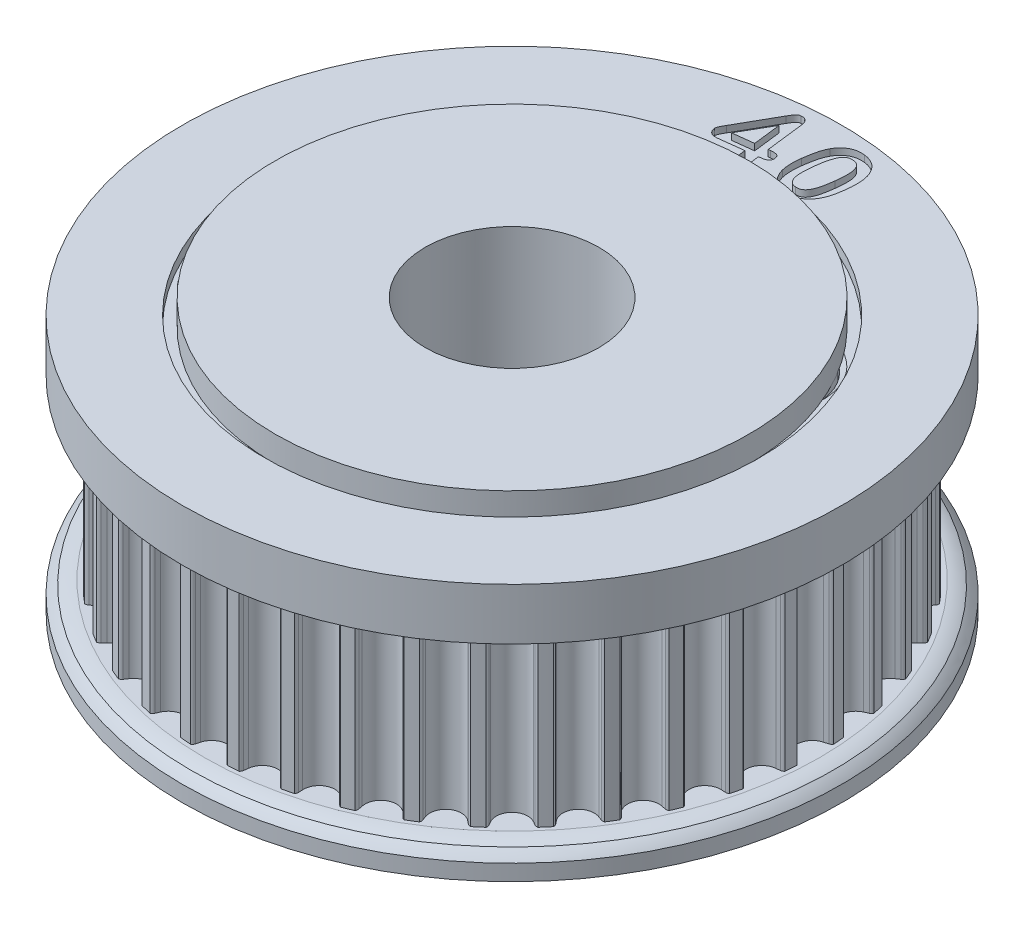
SolidWorks part; units mm, degrees
other "DetailItem2"
material "Markforged"
ref_plane "Front Plane" through (0, 0, 0) normal (0, 0, 1) x (1, 0, 0)
ref_plane "Top Plane" through (0, 0, 0) normal (0, 1, 0) x (1, 0, 0)
ref_plane "Right Plane" through (0, 0, 0) normal (1, 0, 0) x (0, 0, -1)
ref_axis "Centerline" through (0, 8.7312, 0) along (0, -1, 0)
sketch "Sketch1" plane through (0, 0, 0) normal (0, 1, 0) x (1, 0, 0)
  circle A0 centre (0, 0) radius 18.7176
  dimension "OuterDiameter" = 37.4352
extrude "ToothOD" add sketch "Sketch1" along normal mid plane 12.3825
sketch "Sketch2" plane through (0, 0, 0) normal (0, 1, 0) x (1, 0, 0)
  line L0 (0, 17.5492) -> (50000, 17.5492) construction
  line L1 (0, 18.7176) -> (50000, 18.7176) construction
  line L2 (0, 0) -> (0, 50000) construction
  arc A0 (-0.937, 18.2677) -> (0, 17.5492) centre (0, 18.5195) ccw
  arc A1 (-1.1278, 18.6836) -> (1.1278, 18.6836) centre (0, 0) cw
  circle A2 centre (0, 0) radius 18.7176 construction
  arc A3 (-0.937, 18.2677) -> (-1.0078, 18.5195) centre (-11.9754, 15.3012) ccw
  arc A4 (-1.0078, 18.5195) -> (-1.1278, 18.6836) centre (-1.2954, 18.4351) ccw
  circle A5 centre (0, 0) radius 18.7176 construction
  arc A6 (0.937, 18.2677) -> (1.0078, 18.5195) centre (11.9754, 15.3012) cw
  arc A7 (1.0078, 18.5195) -> (1.1278, 18.6836) centre (1.2954, 18.4351) cw
  arc A8 (0, 17.5492) -> (0.937, 18.2677) centre (0, 18.5195) ccw
  dimension "D1" = 1.9406
  dimension "D3" = 22.86
  dimension "D4" = 0.5994
  dimension "D2" = 1.1684
  dimension "D5" = 1.2954
extrude "ToothProfile" cut sketch "Sketch2" against normal through all both and the other way through all
pattern_circular "ToothPattern" count 40 over 360 about axis through (0, 6.1913, 0) along (0, -1, 0) of "ToothProfile"
sketch "Sketch4" plane through (0, 0, 0) normal (0, 0, 1) x (1, 0, 0)
  line L0 (0, -6.1913) -> (18.9716, -6.1913)
  line L1 (0, -7.9375) -> (20.32, -7.9375)
  line L2 (0, -7.9375) -> (0, -6.1913)
  line L3 (20.32, -7.9375) -> (20.32, -6.9532)
  line L4 (0, 0) -> (50000, 0) construction
  line L5 (20.32, 7.9375) -> (20.32, 6.9532)
  line L6 (0, 7.9375) -> (0, 6.1913)
  line L7 (0, 7.9375) -> (20.32, 7.9375)
  line L8 (0, 6.1913) -> (18.9716, 6.1913) construction
  line L9 (0, 6.1913) -> (0, 3.9688)
  line L10 (0, 3.9688) -> (18.9716, 3.9688)
  line L11 (18.9716, 3.9688) -> (20.32, 4.7473)
  line L12 (20.32, 4.7473) -> (20.32, 6.9532)
  line L13 (18.9716, 3.9688) -> (18.9716, 6.1913) construction
  arc A0 (18.9716, -6.1913) -> (19.812, -6.4452) centre (18.6641, -8.7261) cw
  arc A2 (19.812, -6.4452) -> (20.32, -6.9532) centre (17.815, -8.9503) cw
  arc A3 (19.812, 6.4452) -> (20.32, 6.9532) centre (17.815, 8.9503) ccw construction
  arc A4 (18.9716, 6.1913) -> (19.812, 6.4452) centre (18.6641, 8.7261) ccw construction
  dimension "D5" = 2.5534
  dimension "D6" = 3.2036
  dimension "FlangeID" = 18.9716
  dimension "D1" = 1.7463
  dimension "D2" = 0.9843
  dimension "D3" = 6.1913
  dimension "D4" = 15.875
  dimension "D7" = 0.762
  dimension "D8" = 0.508
  dimension "D10" = 0.508
  dimension "D9" = 20.32
  dimension "D11" = 10.16
  dimension "D12" = 30
revolve "Flange" add sketch "Sketch4" angle 360 about axis through (0, 8.7312, 0) along (0, -1, 0)
sketch "Sketch7" plane through (0, 0, 0) normal (0, -1, 0) x (1, 0, 0)
  circle A0 centre (0, 0) radius 5.3581
  dimension "D1" = 10.7163
extrude "Bore" cut sketch "Sketch7" against normal through all both and the other way through all
sketch "Sketch9" plane through (0, 7.9375, 0) normal (0, 1, 0) x (1, 0, 0)
  arc A0 (-10.7763, -10.7763) -> (10.7763, -10.7763) centre (0, 0) cw construction
  text T0 "40" font "Arial Rounded MT Bold" height 4.572
  point P3 (0, 15.24)
  dimension "D1" = 15.24
  dimension "D2" = 270
extrude "Large Tooth Count" cut sketch "Sketch9" against normal blind 0.4 and the other way through all
sketch "Sketch11" plane through (0, 7.9375, 0) normal (0, 1, 0) x (1, 0, 0)
  arc A0 (-4.8314, -4.8314) -> (4.8314, -4.8314) centre (0, 0) cw construction
  text T0 "<b>40</b>" font "Arial Rounded MT Bold" height 2.286
  point P6 (0, 6.8326)
  dimension "D4" = 6.8326
  dimension "D3" = 270
extrude "Small Tooth Count" [suppressed] cut sketch "Sketch11" against normal blind 0.4 and the other way through all
sketch "Sketch14" plane through (0, 0, 0) normal (0, 0, 1) x (1, 0, 0)
  line L0 (20.32, 7.9375) -> (-20.32, 7.9375) construction
  line L1 (0, 7.9375) -> (15.24, 7.9375)
  line L2 (0, 7.9375) -> (0, 7.3025)
  line L3 (0, 7.3025) -> (15.24, 7.3025)
  line L4 (15.24, 7.9375) -> (15.24, 7.3025)
  line L5 (0, 7.9375) -> (15.24, 7.3025) construction
  line L6 (0, 7.3025) -> (15.24, 7.9375) construction
  line L7 (-20.32, -7.9375) -> (20.32, -7.9375) construction
  line L8 (0, -7.9375) -> (15.24, -7.9375)
  line L9 (0, -7.9375) -> (0, -2.2225)
  line L10 (0, -2.2225) -> (15.24, -2.2225)
  line L11 (15.24, -7.9375) -> (15.24, -2.2225)
  line L12 (0, -7.9375) -> (15.24, -2.2225) construction
  line L13 (0, -2.2225) -> (15.24, -7.9375) construction
  line L14 (0, 0) -> (0, 50000) construction
  point P4 (7.62, 7.62)
  point P11 (7.62, -5.08)
  dimension "D1" = 9.525
  dimension "D2" = 15.24
  dimension "D3" = 10.16
revolve "Cut-Revolve1" cut sketch "Sketch14" angle 360 about L14
sketch "Sketch15" plane through (0, -7.9375, 0) normal (0, -1, 0) x (1, 0, 0)
  line L0 (0, 0) -> (0, 11.43) construction
  line L1 (-3.175, 0) -> (-3.175, 11.43)
  line L2 (3.175, 0) -> (3.175, 11.43)
  arc A0 (-3.175, 0) -> (3.175, 0) centre (0, 0) ccw
  arc A1 (3.175, 11.43) -> (-3.175, 11.43) centre (0, 11.43) ccw
  point P3 (0, 5.715)
  dimension "D1" = 3.175
  dimension "D2" = 11.43
extrude "Cut-Extrude1" cut sketch "Sketch15" against normal through all
pattern_circular "CirPattern1" count 6 over 360 about axis through (0, 7.9375, 0) along (0, -1, 0) of "Cut-Extrude1"
fillet "Fillet1" radius 3.175 6 edges at (-6.35, 2.54, 0) (-3.175, 2.54, -5.4993) (3.175, 2.54, -5.4993) (6.35, 2.54, 0) (-3.175, 2.54, 5.4993) (3.175, 2.54, 5.4993)
sketch "Sketch17" plane through (0, -2.2225, 0) normal (0, -1, 0) x (1, 0, 0)
  line L14 (3.175, 10.9985) -> (3.175, 11.43)
  line L16 (8.3112, 8.4646) -> (7.9375, 8.2489)
  line L18 (11.1125, 2.7496) -> (11.4862, 2.9654)
  line L20 (11.4862, -2.9654) -> (11.1125, -2.7496)
  line L22 (7.9375, -8.2489) -> (8.3112, -8.4646)
  line L24 (3.175, -11.43) -> (3.175, -10.9985)
  line L26 (-3.175, -10.9985) -> (-3.175, -11.43)
  line L28 (-8.3112, -8.4646) -> (-7.9375, -8.2489)
  line L30 (-11.1125, -2.7496) -> (-11.4862, -2.9654)
  line L32 (-11.4862, 2.9654) -> (-11.1125, 2.7496)
  line L34 (-7.9375, 8.2489) -> (-8.3112, 8.4646)
  line L37 (-3.175, 11.43) -> (-3.175, 10.9985)
  line L50 (3.175, 10.9985) -> (3.175, 11.43)
  line L51 (8.3112, 8.4646) -> (7.9375, 8.2489)
  line L52 (11.1125, 2.7496) -> (11.4862, 2.9654)
  line L53 (11.4862, -2.9654) -> (11.1125, -2.7496)
  line L54 (7.9375, -8.2489) -> (8.3112, -8.4646)
  line L55 (3.175, -11.43) -> (3.175, -10.9985)
  line L56 (-3.175, -10.9985) -> (-3.175, -11.43)
  line L57 (-8.3112, -8.4646) -> (-7.9375, -8.2489)
  line L58 (-11.1125, -2.7496) -> (-11.4862, -2.9654)
  line L59 (-11.4862, 2.9654) -> (-11.1125, 2.7496)
  line L60 (-7.9375, 8.2489) -> (-8.3112, 8.4646)
  line L61 (-3.175, 11.43) -> (-3.175, 10.9985)
  circle A1 centre (0, 0) radius 5.3581 construction
  circle A8 centre (0, 0) radius 5.3581
  arc A47 (3.175, 10.9985) -> (7.9375, 8.2489) centre (6.35, 10.9985) ccw
  arc A48 (11.4862, 2.9654) -> (8.3112, 8.4646) centre (9.8987, 5.715) ccw
  arc A49 (11.1125, 2.7496) -> (11.1125, -2.7496) centre (12.7, 0) ccw
  arc A50 (8.3112, -8.4646) -> (11.4862, -2.9654) centre (9.8987, -5.715) ccw
  arc A51 (7.9375, -8.2489) -> (3.175, -10.9985) centre (6.35, -10.9985) ccw
  arc A52 (-3.175, -11.43) -> (3.175, -11.43) centre (0, -11.43) ccw
  arc A53 (-3.175, -10.9985) -> (-7.9375, -8.2489) centre (-6.35, -10.9985) ccw
  arc A54 (-11.4862, -2.9654) -> (-8.3112, -8.4646) centre (-9.8987, -5.715) ccw
  arc A55 (-11.1125, -2.7496) -> (-11.1125, 2.7496) centre (-12.7, 0) ccw
  arc A56 (-8.3112, 8.4646) -> (-11.4862, 2.9654) centre (-9.8987, 5.715) ccw
  arc A57 (-7.9375, 8.2489) -> (-3.175, 10.9985) centre (-6.35, 10.9985) ccw
  arc A70 (3.175, 11.43) -> (-3.175, 11.43) centre (0, 11.43) ccw
  arc A71 (3.175, 10.9985) -> (7.9375, 8.2489) centre (6.35, 10.9985) ccw
  arc A72 (11.4862, 2.9654) -> (8.3112, 8.4646) centre (9.8987, 5.715) ccw
  arc A73 (11.1125, 2.7496) -> (11.1125, -2.7496) centre (12.7, 0) ccw
  arc A74 (8.3112, -8.4646) -> (11.4862, -2.9654) centre (9.8987, -5.715) ccw
  arc A75 (7.9375, -8.2489) -> (3.175, -10.9985) centre (6.35, -10.9985) ccw
  arc A76 (-3.175, -11.43) -> (3.175, -11.43) centre (0, -11.43) ccw
  arc A77 (-3.175, -10.9985) -> (-7.9375, -8.2489) centre (-6.35, -10.9985) ccw
  arc A78 (-11.4862, -2.9654) -> (-8.3112, -8.4646) centre (-9.8987, -5.715) ccw
  arc A79 (-11.1125, -2.7496) -> (-11.1125, 2.7496) centre (-12.7, 0) ccw
  arc A80 (-8.3112, 8.4646) -> (-11.4862, 2.9654) centre (-9.8987, 5.715) ccw
  arc A81 (-7.9375, 8.2489) -> (-3.175, 10.9985) centre (-6.35, 10.9985) ccw
  arc A82 (3.175, 11.43) -> (-3.175, 11.43) centre (0, 11.43) ccw
  dimension "D1" = 0
extrude "Boss-Extrude1" add sketch "Sketch17" against normal up to surface (9.525 mm away) separate body up to face at (0, 7.3025, 0)
sketch "Sketch21" plane through (0, -2.2225, 0) normal (0, -1, 0) x (1, 0, 0)
  circle A0 centre (0, 0) radius 7.9375
  dimension "D1" = 15.875
extrude "Cut-Extrude4" cut sketch "Sketch21" against normal blind 2.286
chamfer "Chamfer1" distance 2.54 angle 45 1 edges at (0, -7.9375, -15.24)
chamfer "Chamfer2" distance 0.635 angle 45 1 edges at (0, -2.2225, -15.24)
sketch "Sketch22" plane through (0, 7.3025, 0) normal (0, 1, 0) x (1, 0, 0)
  circle A0 centre (0, 0) radius 5.3581
  circle A1 centre (0, 0) radius 14.605
  arc A2 (8.3112, -8.4646) -> (11.4862, -2.9654) centre (9.8987, -5.715) ccw construction
  circle A3 centre (0, 0) radius 5.3581 construction
extrude "Boss-Extrude2" add sketch "Sketch22" along normal blind 1.5875 separate body
combine bodies "Combine1" operation type add bodies to combine 118 117
sketch "Sketch23" plane through (0, 7.3025, 0) normal (0, 1, 0) x (1, 0, 0)
  line L0 (7.9058, -8.3039) -> (8.2794, -8.5196)
  line L1 (11.5179, -2.9104) -> (11.1442, -2.6946)
  line L2 (11.1442, 2.6946) -> (11.5179, 2.9104)
  line L3 (8.2794, 8.5196) -> (7.9057, 8.3039)
  line L4 (3.2385, 10.9985) -> (3.2385, 11.43)
  line L5 (-3.2385, 11.43) -> (-3.2385, 10.9985)
  line L6 (-7.9058, 8.3039) -> (-8.2794, 8.5196)
  line L7 (-11.5179, 2.9104) -> (-11.1442, 2.6946)
  line L8 (-11.1442, -2.6946) -> (-11.5179, -2.9104)
  line L9 (-8.2794, -8.5196) -> (-7.9057, -8.3039)
  line L10 (-3.2385, -10.9985) -> (-3.2385, -11.43)
  line L11 (3.2385, -11.43) -> (3.2385, -10.9985)
  line L12 (7.9375, -8.2489) -> (8.3112, -8.4646)
  line L13 (3.175, -11.43) -> (3.175, -10.9985)
  line L14 (-3.175, -10.9985) -> (-3.175, -11.43)
  line L15 (-8.3112, -8.4646) -> (-7.9375, -8.2489)
  line L16 (-11.1125, -2.7496) -> (-11.4862, -2.9654)
  line L17 (-11.4862, 2.9654) -> (-11.1125, 2.7496)
  line L18 (-7.9375, 8.2489) -> (-8.3112, 8.4646)
  line L19 (-3.175, 11.43) -> (-3.175, 10.9985)
  line L20 (3.175, 10.9985) -> (3.175, 11.43)
  line L21 (8.3112, 8.4646) -> (7.9375, 8.2489)
  line L22 (11.1125, 2.7496) -> (11.4862, 2.9654)
  line L23 (11.4862, -2.9654) -> (11.1125, -2.7496)
  line L24 (7.9375, -8.2489) -> (8.3112, -8.4646)
  line L25 (3.175, -11.43) -> (3.175, -10.9985)
  line L26 (-3.175, -10.9985) -> (-3.175, -11.43)
  line L27 (-8.3112, -8.4646) -> (-7.9375, -8.2489)
  line L28 (-11.1125, -2.7496) -> (-11.4862, -2.9654)
  line L29 (-11.4862, 2.9654) -> (-11.1125, 2.7496)
  line L30 (-7.9375, 8.2489) -> (-8.3112, 8.4646)
  line L31 (-3.175, 11.43) -> (-3.175, 10.9985)
  line L32 (3.175, 10.9985) -> (3.175, 11.43)
  line L33 (8.3112, 8.4646) -> (7.9375, 8.2489)
  line L34 (11.1125, 2.7496) -> (11.4862, 2.9654)
  line L35 (11.4862, -2.9654) -> (11.1125, -2.7496)
  arc A0 (8.2794, -8.5196) -> (11.5179, -2.9104) centre (9.8987, -5.715) ccw
  arc A1 (11.1442, 2.6946) -> (11.1442, -2.6946) centre (12.7, 0) ccw
  arc A2 (11.5179, 2.9104) -> (8.2794, 8.5196) centre (9.8987, 5.715) ccw
  arc A3 (3.2385, 10.9985) -> (7.9057, 8.3039) centre (6.35, 10.9985) ccw
  arc A4 (3.2385, 11.43) -> (-3.2385, 11.43) centre (0, 11.43) ccw
  arc A5 (-7.9058, 8.3039) -> (-3.2385, 10.9985) centre (-6.35, 10.9985) ccw
  arc A6 (-8.2794, 8.5196) -> (-11.5179, 2.9104) centre (-9.8987, 5.715) ccw
  arc A7 (-11.1442, -2.6946) -> (-11.1442, 2.6946) centre (-12.7, 0) ccw
  arc A8 (-11.5179, -2.9104) -> (-8.2794, -8.5196) centre (-9.8987, -5.715) ccw
  arc A9 (-3.2385, -10.9985) -> (-7.9057, -8.3039) centre (-6.35, -10.9985) ccw
  arc A10 (-3.2385, -11.43) -> (3.2385, -11.43) centre (0, -11.43) ccw
  arc A11 (7.9058, -8.3039) -> (3.2385, -10.9985) centre (6.35, -10.9985) ccw
  arc A12 (7.9375, -8.2489) -> (3.175, -10.9985) centre (6.35, -10.9985) ccw
  arc A13 (-3.175, -11.43) -> (3.175, -11.43) centre (0, -11.43) ccw
  arc A14 (-3.175, -10.9985) -> (-7.9375, -8.2489) centre (-6.35, -10.9985) ccw
  arc A15 (-11.4862, -2.9654) -> (-8.3112, -8.4646) centre (-9.8987, -5.715) ccw
  arc A16 (-11.1125, -2.7496) -> (-11.1125, 2.7496) centre (-12.7, 0) ccw
  arc A17 (-8.3112, 8.4646) -> (-11.4862, 2.9654) centre (-9.8987, 5.715) ccw
  arc A18 (-7.9375, 8.2489) -> (-3.175, 10.9985) centre (-6.35, 10.9985) ccw
  arc A19 (3.175, 11.43) -> (-3.175, 11.43) centre (0, 11.43) ccw
  arc A20 (3.175, 10.9985) -> (7.9375, 8.2489) centre (6.35, 10.9985) ccw
  arc A21 (11.4862, 2.9654) -> (8.3112, 8.4646) centre (9.8987, 5.715) ccw
  arc A22 (11.1125, 2.7496) -> (11.1125, -2.7496) centre (12.7, 0) ccw
  arc A23 (8.3112, -8.4646) -> (11.4862, -2.9654) centre (9.8987, -5.715) ccw
  arc A24 (7.9375, -8.2489) -> (3.175, -10.9985) centre (6.35, -10.9985) ccw
  arc A25 (-3.175, -11.43) -> (3.175, -11.43) centre (0, -11.43) ccw
  arc A26 (-3.175, -10.9985) -> (-7.9375, -8.2489) centre (-6.35, -10.9985) ccw
  arc A27 (-11.4862, -2.9654) -> (-8.3112, -8.4646) centre (-9.8987, -5.715) ccw
  arc A28 (-11.1125, -2.7496) -> (-11.1125, 2.7496) centre (-12.7, 0) ccw
  arc A29 (-8.3112, 8.4646) -> (-11.4862, 2.9654) centre (-9.8987, 5.715) ccw
  arc A30 (-7.9375, 8.2489) -> (-3.175, 10.9985) centre (-6.35, 10.9985) ccw
  arc A31 (3.175, 11.43) -> (-3.175, 11.43) centre (0, 11.43) ccw
  arc A32 (3.175, 10.9985) -> (7.9375, 8.2489) centre (6.35, 10.9985) ccw
  arc A33 (11.4862, 2.9654) -> (8.3112, 8.4646) centre (9.8987, 5.715) ccw
  arc A34 (11.1125, 2.7496) -> (11.1125, -2.7496) centre (12.7, 0) ccw
  arc A35 (8.3112, -8.4646) -> (11.4862, -2.9654) centre (9.8987, -5.715) ccw
  dimension "D1" = 0
  dimension "D2" = 0.0635
extrude "Cut-Extrude5" cut sketch "Sketch23" against normal through all
chamfer "Chamfer3" distance 0.3175 angle 45 54 edges at (-4.7942, 7.3025, 8.3039) (-3.2385, 7.3025, 11.2143) (-8.0926, 7.3025, 8.4118) (0, 7.3025, 14.6685) (-12.7033, 7.3025, 7.3342) (3.2385, 7.3025, 11.2143) (-11.3311, 7.3025, 2.8025) (4.7943, 7.3025, 8.3039) (-9.5885, 7.3025, 0) (8.0926, 7.3025, 8.4118) (-11.3311, 7.3025, -2.8025) (12.7033, 7.3025, 7.3343) (-12.7033, 7.3025, -7.3343) (11.3311, 7.3025, 2.8025) (-8.0926, 7.3025, -8.4118) (9.5885, 7.3025, 0) (-4.7943, 7.3025, -8.3039) (11.3311, 7.3025, -2.8025) (-3.2385, 7.3025, -11.2143) (12.7033, 7.3025, -7.3342) (0, 7.3025, -14.6685) (8.0926, 7.3025, -8.4118) (3.2385, 7.3025, -11.2143) (4.7942, 7.3025, -8.3039) (-10.3811, -2.2225, 8.9174) (-2.5321, -2.2225, 13.449) (-8.0926, -2.2225, 8.4118) (-3.2385, -2.2225, 11.2143) (-4.7942, -2.2225, 8.3039) (2.5321, -2.2225, 13.449) (10.3811, -2.2225, 8.9174) (3.2385, -2.2225, 11.2143) (8.0926, -2.2225, 8.4118) (4.7943, -2.2225, 8.3039) (12.9132, -2.2225, 4.5316) (12.9132, -2.2225, -4.5316) (11.3311, -2.2225, 2.8025) (11.3311, -2.2225, -2.8025) (9.5885, -2.2225, 0) (10.3811, -2.2225, -8.9174) (2.5321, -2.2225, -13.449) (8.0926, -2.2225, -8.4118) (3.2385, -2.2225, -11.2143) (4.7942, -2.2225, -8.3039) (-2.5321, -2.2225, -13.449) (-10.3811, -2.2225, -8.9174) (-3.2385, -2.2225, -11.2143) (-8.0926, -2.2225, -8.4118) (-4.7943, -2.2225, -8.3039) (-12.9132, -2.2225, -4.5316) (-12.9132, -2.2225, 4.5316) (-11.3311, -2.2225, -2.8025) (-11.3311, -2.2225, 2.8025) (-9.5885, -2.2225, 0)
delete or keep bodies "Body-Delete/Keep 1" [suppressed] bodies 119
delete or keep bodies "Body-Delete/Keep 2" [suppressed] type keep bodies bodies 120
delete or keep bodies "Body-Delete/Keep 3" [suppressed] type keep bodies bodies 118
equation "\"OuterDiameter@Sketch1\"= \"OD\""
equation "\"Teeth\"= \"No_Teeth\""
equation "\"PD\"= \"No_Teeth\" * 3mm / pi"
equation "\"OD\"= \"PD\" - .030"
equation "\"ToothCount@ToothPattern\" = \"Teeth\""
equation "\"Angle\"= 360 / \"Teeth\""
equation "\"AngleSpacing@ToothPattern\" = \"Angle\""
equation "\"FlangeID@Sketch4\"=\"OD\"/2+.01"
equation "\"D3@Sketch4\"=\"Tooth_Face_Length\"/2"
equation "\"Bearing_Feature\"= \"Bearing_Boss\""
equation "\"TopBearingBoss\" = IIF ( \"Bearing_Feature\" > 0 , \"unsuppressed\" , \"suppressed\" )"
equation "\"HexBore\"= \"Hex_Bore\" + \"Print_Tolerance\""
equation "\"Large Tooth Count\" = iif ( \"No_Teeth\" < \"TextTooth\" , \"suppressed\" , \"unsuppressed\" )"
equation "\"Small Tooth Count\"= iif ( \"No_Teeth\" < \"TextTooth\" , \"unsuppressed\" , \"suppressed\" )"
equation "\"BottomBearingBoss\" = iif ( \"Bearing_Feature\" > 1 , \"unsuppressed\" , \"suppressed\" )"
equation "\"ToothFaceLength@ToothOD\" = \"Tooth_Face_Length\""
equation "\"D4@Sketch4\" = \"Width_No_BearingBoss\""
equation "\"TextTooth\"= iif ( \"Hex_Bore\" <= .380 , 23 , iif ( \"Hex_Bore\" <= .505 , 25 , 16 ) )"
equation "\"D4@Sketch11\"=\"HexBore\"/2+.08"
